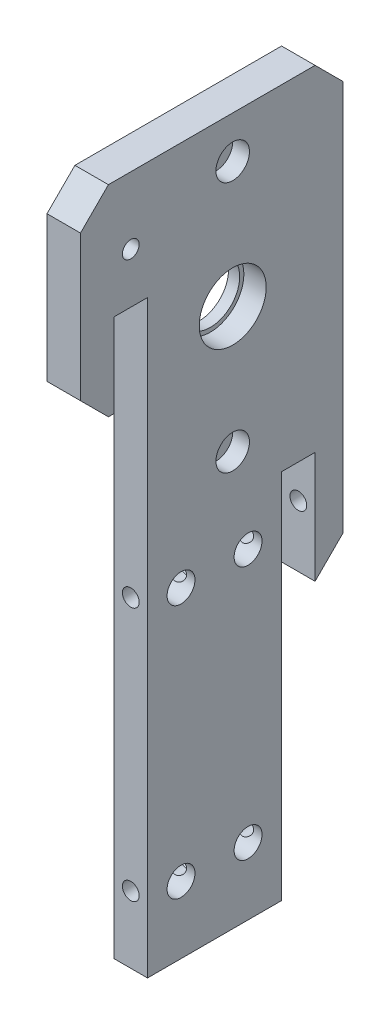
SolidWorks part; units mm, degrees
material "HDPE-green"
ref_plane "Front Plane" through (0, 0, 0) normal (0, 0, 1) x (1, 0, 0)
ref_plane "Top Plane" through (0, 0, 0) normal (0, 1, 0) x (1, 0, 0)
ref_plane "Right Plane" through (0, 0, 0) normal (1, 0, 0) x (0, 0, -1)
sketch "Sketch1" plane through (0, 0, 0) normal (1, 0, 0) x (0, 0, -1)
  line L1 (-29.5, 60) -> (29.5, 60)
  line L2 (-29.5, 60) -> (-29.5, -60)
  line L3 (-29.5, -60) -> (29.5, -60)
  line L4 (29.5, 60) -> (29.5, -60)
  line L5 (-29.5, 60) -> (29.5, -60) construction
  line L6 (-29.5, -60) -> (29.5, 60) construction
  circle A0 centre (0, 0) radius 10.5
  point P0 (0, 0)
  dimension "D3" = 21
  dimension "D1" = 59
  dimension "D2" = 120
extrude "Boss-Extrude1" add sketch "Sketch1" along normal blind 12
sketch "Sketch8" plane through (0, 0, 0) normal (-1, 0, 0) x (0, 0, 1)
  line L2 (42.5, 18) -> (42.5, -12)
  line L3 (42.5, -12) -> (54.5, -12)
  line L4 (54.5, -12) -> (54.5, 60)
  line L5 (54.5, 60) -> (29.5, 60)
  line L7 (29.5, 60) -> (29.5, -60)
  line L9 (29.5, -60) -> (30.5, -60)
  line L10 (30.5, -60) -> (30.5, 18)
  line L11 (30.5, 18) -> (42.5, 18)
  dimension "D1" = 72
  dimension "D2" = 1
  dimension "D3" = 12
  dimension "D4" = 30
extrude "Boss-Extrude2" add sketch "Sketch8" against normal blind 12
sketch "Sketch9" plane through (0, 0, 0) normal (-1, 0, 0) x (0, 0, 1)
  line L0 (-29.5, -60) -> (-29.5, 60) construction
  line L1 (30.5, -60) -> (-17.5, -60)
  line L2 (30.5, -60) -> (30.5, -193)
  line L3 (30.5, -193) -> (-17.5, -193)
  line L4 (-17.5, -60) -> (-17.5, -193)
  dimension "D1" = 12
  dimension "D2" = 133
  dimension "D3" = 48
extrude "Boss-Extrude3" add sketch "Sketch9" against normal blind 12
sketch "Sketch11" plane through (12, 0, 0) normal (1, 0, 0) x (0, 0, -1)
  line L1 (29.5, 60) -> (39.5, 60)
  line L2 (29.5, 60) -> (29.5, -100)
  line L3 (29.5, -100) -> (39.5, -100)
  line L4 (39.5, 60) -> (39.5, -100)
  dimension "D1" = 10
  dimension "D2" = 160
extrude "Boss-Extrude4" add sketch "Sketch11" against normal blind 12
chamfer "Chamfer1" distance 10 angle 45 3 edges at (6, 60, -39.5) (6, 60, 54.5) (6, -12, 54.5)
chamfer "Chamfer2" distance 10 angle 45 1 edges at (6, -100, -39.5)
hole_wizard "Ø10.0 (10) Diameter Hole1" positions "Sketch14" profile "Sketch13" hole size "Ø10.0" standard "ISO" end condition up to next
sketch "Sketch14" plane through (12, 0, 0) normal (1, 0, 0) x (0, 0, -1)
  line L0 (17.5, -193) -> (-30.5, -193) construction
  line L2 (17.5, -60) -> (17.5, -193) construction
  line L3 (-30.5, -193) -> (-30.5, 18) construction
  point P0 (-18.5, -169)
  point P1 (5.5, -169)
  point P3 (-18.5, -78)
  point P13 (5.5, -78)
  dimension "D1" = 24
  dimension "D2" = 24
  dimension "D3" = 12
  dimension "D4" = 12
  dimension "D5" = 12
  dimension "D6" = 12
  dimension "D7" = 115
  dimension "D8" = 115
sketch "Sketch13" plane through (12, -169, 18.5) normal (0, 1, 0) x (0, 0, -1)
  line L0 (0, 0) -> (0, 12)
  line L1 (0, 12) -> (5, 12)
  line L2 (5, 12) -> (5, 0)
  line L5 (5, 0) -> (0, 0)
  line L11 (0, -6.35) -> (0, 107.95) construction
  dimension "Thru Hole Dia." = 10
  dimension "Thru Hole Depth" = 12
hole_wizard "Ø6.0 (6) Diameter Hole1" positions "Sketch16" profile "Sketch15" hole size "Ø6.0" standard "ISO"
sketch "Sketch16" plane through (0, 0, -17.5) normal (0, 0, -1) x (-1, 0, 0)
  line L0 (-12, -60) -> (-12, -193) construction
  line L2 (-12, -193) -> (0, -193) construction
  point P0 (-6, -169)
  point P7 (-6, -78)
  dimension "D1" = 6
  dimension "D2" = 24
  dimension "D3" = 115
sketch "Sketch15" plane through (6, -169, -17.5) normal (1, 0, 0) x (0, 1, 0)
  line L0 (0, 0) -> (0, 21.8026)
  line L1 (0, 21.8026) -> (3, 20)
  line L2 (3, 20) -> (3, 0)
  line L5 (3, 0) -> (0, 0)
  line L10 (0, 21.8026) -> (-3, 20) construction
  line L11 (0, -6.35) -> (0, 107.95) construction
  dimension "Hole Dia." = 6
  dimension "Hole Depth" = 20
  dimension "Drill Angle" = 118
hole_wizard "Ø6.0 (6) Diameter Hole3" positions "Sketch20" profile "Sketch19" hole size "Ø6.0" standard "ISO"
sketch "Sketch20" plane through (0, 0, -39.5) normal (0, 0, -1) x (-1, 0, 0)
  line L0 (-12, -90) -> (-12, 50) construction
  line L1 (-12, -193) -> (0, -193) construction
  point P0 (-6, -78)
  dimension "D1" = 6
  dimension "D2" = 115
sketch "Sketch19" plane through (6, -78, -39.5) normal (1, 0, 0) x (0, 1, 0)
  line L0 (0, 0) -> (0, 21.8026)
  line L1 (0, 21.8026) -> (3, 20)
  line L2 (3, 20) -> (3, 0)
  line L5 (3, 0) -> (0, 0)
  line L10 (0, 21.8026) -> (-3, 20) construction
  line L11 (0, -6.35) -> (0, 107.95) construction
  dimension "Hole Dia." = 6
  dimension "Hole Depth" = 20
  dimension "Drill Angle" = 118
hole_wizard "Ø6.0 (6) Diameter Hole4" positions "Sketch22" profile "Sketch21" hole size "Ø6.0" standard "ISO" end condition up to next
sketch "Sketch22" plane through (12, 0, 0) normal (1, 0, 0) x (0, 0, -1)
  line L1 (29.5, 60) -> (-44.5, 60) construction
  line L2 (-30.5, -193) -> (-30.5, 18) construction
  point P0 (-36.5, 36)
  dimension "D1" = 6
  dimension "D2" = 24
sketch "Sketch21" plane through (12, 36, 36.5) normal (0, 1, 0) x (0, 0, -1)
  line L0 (0, 0) -> (0, 12)
  line L1 (0, 12) -> (3, 12)
  line L2 (3, 12) -> (3, 0)
  line L5 (3, 0) -> (0, 0)
  line L11 (0, -6.35) -> (0, 107.95) construction
  dimension "Thru Hole Dia." = 6
  dimension "Thru Hole Depth" = 12
hole_wizard "Ø6.0 (6) Diameter Hole5" positions "Sketch24" profile "Sketch23" hole size "Ø6.0" standard "ISO"
sketch "Sketch24" plane through (0, 0, 30.5) normal (0, 0, 1) x (1, 0, 0)
  line L0 (12, -193) -> (0, -193) construction
  line L1 (12, -193) -> (12, 18) construction
  point P0 (6, -78)
  point P1 (6, -169)
  dimension "D1" = 24
  dimension "D2" = 6
  dimension "D3" = 115
  dimension "D4" = 6
sketch "Sketch23" plane through (6, -78, 30.5) normal (1, 0, 0) x (0, -1, 0)
  line L0 (0, 0) -> (0, 21.8026)
  line L1 (0, 21.8026) -> (3, 20)
  line L2 (3, 20) -> (3, 0)
  line L5 (3, 0) -> (0, 0)
  line L10 (0, 21.8026) -> (-3, 20) construction
  line L11 (0, -6.35) -> (0, 107.95) construction
  dimension "Hole Dia." = 6
  dimension "Hole Depth" = 20
  dimension "Drill Angle" = 118
hole_wizard "Hole2" positions "Sketch26" profile "Sketch25" legacy
sketch "Sketch26" plane through (12, 0, 0) normal (1, 0, 0) x (0, 0, -1)
  circle A0 centre (0, 0) radius 10.5 construction
  point P1 (0, -45)
  point P3 (0, 45)
  dimension "D1" = 45
  dimension "D2" = 45
sketch "Sketch25" plane through (12, -45, 0) normal (0, 1, 0) x (0, 0, -1)
  line L0 (0, 0) -> (0, 6)
  line L1 (0, 6) -> (6, 6)
  line L2 (6, 6) -> (6, 0)
  line L3 (6, 0) -> (0, 0)
  line L4 (0, 110) -> (0, -10) construction
  dimension "Diameter" = 12
  dimension "Depth" = 6
sketch "Sketch27" plane through (12, 0, 0) normal (1, 0, 0) x (0, 0, -1)
  circle A0 centre (0, 0) radius 12
  dimension "D1" = 24
extrude "Cut-Extrude1" cut sketch "Sketch27" against normal blind 8
